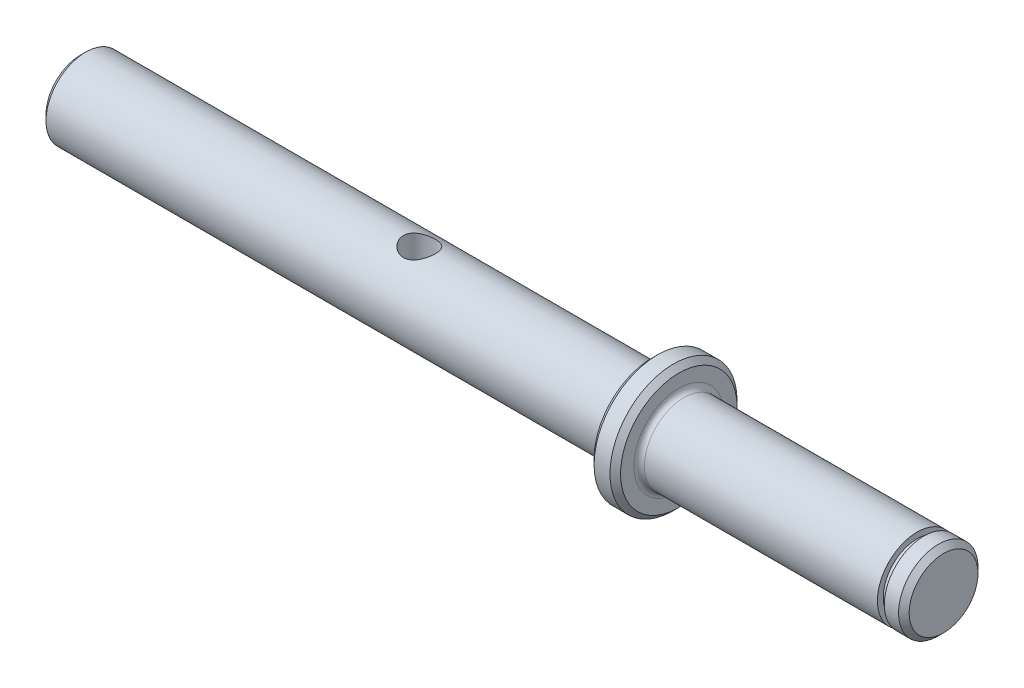
SolidWorks part; units mm, degrees
ref_plane "Front Plane" through (0, 0, 0) normal (0, 0, 1) x (1, 0, 0)
ref_plane "Top Plane" through (0, 0, 0) normal (0, 1, 0) x (1, 0, 0)
ref_plane "Right Plane" through (0, 0, 0) normal (1, 0, 0) x (0, 0, -1)
ref_axis "X" through (-88.99, 0, 0) along (1, 0, 0)
ref_axis "Y" through (0, 0, -88.99) along (0, 0, 1)
ref_axis "Z" through (0, 55, 0) along (0, -1, 0)
sketch "Sketch1" plane through (0, 0, 0) normal (0, 0, 1) x (1, 0, 0)
  line L0 (0, 0) -> (-28.2258, 0) construction
  line L1 (0, 0) -> (0, 7.5)
  line L2 (0, 7.5) -> (108, 7.5)
  line L3 (163, 7.5) -> (163, 0)
  line L4 (163, 0) -> (0, 0)
  line L15 (113, 7.5) -> (158, 7.5)
  line L22 (159.3, 7.5) -> (163, 7.5)
  line L24 (108, 7.5) -> (108, 12)
  line L25 (108, 12) -> (113, 12)
  line L26 (113, 7.5) -> (113, 12)
  line L28 (158, 7.5) -> (158, 6.4)
  line L29 (158, 6.4) -> (159.3, 6.4)
  line L30 (159.3, 7.5) -> (159.3, 6.4)
  dimension "D1" = 15
  dimension "D2" = 163
  dimension "D3" = 50
  dimension "D4" = 5
  dimension "D5" = 12
  dimension "D6" = 45
  dimension "D7" = 1.3
  dimension "D8" = 1.1
revolve "Revolve1" add sketch "Sketch1" angle 360 about L0
ref_plane "Plane1" through (81.5, 0, 0) normal (1, 0, 0) x (0, 0, -1)
sketch "Sketch2" plane through (0, 0, 0) normal (0, 1, 0) x (1, 0, 0)
  line L1 (81.5, -7.15) -> (81.5, 7.15) construction
  circle A0 centre (64, 0) radius 3
  dimension "D1" = 6
  dimension "D2" = 17.5
extrude "Cut-Extrude1" cut sketch "Sketch2" against normal blind 10 and the other way blind 10
chamfer "Chamfer1" distance 1 angle 45 4 edges at (113, 0, -12) (108, 0, -12) (0, 0, -7.5) (163, 0, -7.5)
fillet "Fillet1" radius 2 1 edges at (108, 0, -7.5)
fillet "Fillet2" radius 1 1 edges at (113, 0, -7.5)
